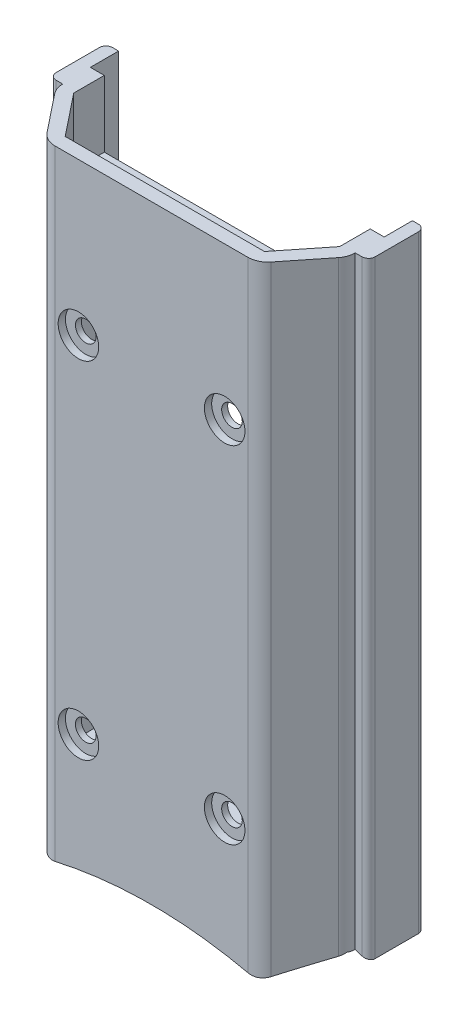
SolidWorks part; units mm, degrees
ref_plane "前视基准面" through (0, 0, 0) normal (0, 0, 1) x (1, 0, 0)
ref_plane "上视基准面" through (0, 0, 0) normal (0, 1, 0) x (1, 0, 0)
ref_plane "右视基准面" through (0, 0, 0) normal (1, 0, 0) x (0, 0, -1)
other "Configuration Table"
sketch "草图1" plane through (0, 0, 0) normal (0, 1, 0) x (1, 0, 0)
  line L5 (21.3466, -10.7196) -> (16.852, -16.3628)
  line L7 (20, -4.6001) -> (22, -4.6001)
  line L9 (20, -9.2001) -> (20, -4.6001)
  line L10 (14.9873, -15.4937) -> (20, -9.2001)
  line L11 (14.5054, -17.4937) -> (-14.5054, -17.4937)
  line L12 (-14.9873, -15.4937) -> (14.9873, -15.4937)
  line L14 (-20, -9.2001) -> (-14.9873, -15.4937)
  line L15 (-20, -4.6001) -> (-20, -9.2001)
  line L17 (-22.1, -0.3496) -> (-23, -0.3496)
  line L18 (-24, -1.3496) -> (-24, -7.8505)
  line L20 (-22, -4.6001) -> (-22.1, -4.6001)
  line L21 (-22.1, -4.6001) -> (-22.1, -0.3496)
  line L22 (22.1, -0.3496) -> (23, -0.3496)
  line L23 (24, -1.3496) -> (24, -7.8505)
  line L41 (22, -4.6001) -> (22.1, -4.6001)
  line L42 (22.1, -4.6001) -> (22.1, -0.3496)
  line L43 (-16.852, -16.3628) -> (-21.3466, -10.7196)
  line L57 (-22, -4.6001) -> (-20, -4.6001)
  line L59 (-22, -8.8505) -> (-23, -8.8505)
  line L61 (22, -8.8505) -> (23, -8.8505)
  arc A2 (23, -8.8505) -> (24, -7.8505) centre (23, -7.8505) ccw
  arc A3 (24, -1.3496) -> (23, -0.3496) centre (23, -1.3496) ccw
  arc A12 (16.852, -16.3628) -> (14.5054, -17.4937) centre (14.5054, -14.4937) cw
  arc A14 (-14.5054, -17.4937) -> (-16.852, -16.3628) centre (-14.5054, -14.4937) cw
  arc A16 (-23, -8.8505) -> (-24, -7.8505) centre (-23, -7.8505) cw
  arc A17 (-23, -0.3496) -> (-24, -1.3496) centre (-23, -1.3496) ccw
  arc A19 (21.3466, -10.7196) -> (22, -8.8505) centre (19, -8.8505) ccw
  arc A20 (-22, -8.8505) -> (-21.3466, -10.7196) centre (-19, -8.8505) ccw
  dimension "D3" = 0.1
  dimension "D2" = 0.1
extrude "凸台-拉伸1" add sketch "草图1" along normal up to surface (58.8974 mm away)
sketch "草图2" plane through (0, 0, 0) normal (0, -1, 0) x (1, 0, 0)
  line L18 (23, 8.8505) -> (22, 8.8505)
  line L19 (-24, 7.8505) -> (-24, 1.3496)
  line L20 (-23, 0.3496) -> (-22.1, 0.3496)
  line L21 (-22.1, 0.3496) -> (-22.1, 4.6001)
  line L22 (-22.1, 4.6001) -> (-20, 4.6001)
  line L23 (-20, 4.6001) -> (-20, 9.2001)
  line L24 (-20, 9.2001) -> (-14.9873, 15.4937)
  line L25 (-14.9873, 15.4937) -> (14.9873, 15.4937)
  line L26 (14.9873, 15.4937) -> (20, 9.2001)
  line L27 (20, 9.2001) -> (20, 4.6001)
  line L28 (20, 4.6001) -> (22.1, 4.6001)
  line L29 (22.1, 4.6001) -> (22.1, 0.3496)
  line L30 (22.1, 0.3496) -> (23, 0.3496)
  line L31 (24, 1.3496) -> (24, 7.8505)
  line L32 (23, 8.8505) -> (22, 8.8505)
  line L33 (21.3466, 10.7196) -> (16.852, 16.3628)
  line L34 (14.5054, 17.4937) -> (-14.5054, 17.4937)
  line L37 (-24, 7.8505) -> (-24, 1.3496)
  line L38 (-23, 0.3496) -> (-22.1, 0.3496)
  line L39 (-22.1, 0.3496) -> (-22.1, 4.6001)
  line L40 (-22.1, 4.6001) -> (-20, 4.6001)
  line L41 (-20, 4.6001) -> (-20, 9.2001)
  line L42 (-20, 9.2001) -> (-14.9873, 15.4937)
  line L43 (-14.9873, 15.4937) -> (14.9873, 15.4937)
  line L44 (14.9873, 15.4937) -> (20, 9.2001)
  line L45 (20, 9.2001) -> (20, 4.6001)
  line L46 (20, 4.6001) -> (22.1, 4.6001)
  line L47 (22.1, 4.6001) -> (22.1, 0.3496)
  line L48 (22.1, 0.3496) -> (23, 0.3496)
  line L49 (24, 1.3496) -> (24, 7.8505)
  line L51 (21.3466, 10.7196) -> (16.852, 16.3628)
  line L52 (14.5054, 17.4937) -> (-14.5054, 17.4937)
  line L57 (-16.852, 16.3628) -> (-21.3466, 10.7196)
  line L58 (-16.852, 16.3628) -> (-21.3466, 10.7196)
  line L61 (-22, 8.8505) -> (-23, 8.8505)
  line L62 (-22, 8.8505) -> (-23, 8.8505)
  arc A8 (-21.3466, 10.7196) -> (-22, 8.8505) centre (-19, 8.8505) ccw
  arc A9 (-21.3466, 10.7196) -> (-22, 8.8505) centre (-19, 8.8505) ccw
  arc A10 (22, 8.8505) -> (21.3466, 10.7196) centre (19, 8.8505) ccw
  arc A11 (22, 8.8505) -> (21.3466, 10.7196) centre (19, 8.8505) ccw
  arc A12 (-23, 8.8505) -> (-24, 7.8505) centre (-23, 7.8505) ccw
  arc A13 (-24, 1.3496) -> (-23, 0.3496) centre (-23, 1.3496) ccw
  arc A14 (23, 0.3496) -> (24, 1.3496) centre (23, 1.3496) ccw
  arc A15 (24, 7.8505) -> (23, 8.8505) centre (23, 7.8505) ccw
  arc A18 (16.852, 16.3628) -> (14.5054, 17.4937) centre (14.5054, 14.4937) ccw
  arc A19 (-14.5054, 17.4937) -> (-16.852, 16.3628) centre (-14.5054, 14.4937) ccw
  arc A22 (-23, 8.8505) -> (-24, 7.8505) centre (-23, 7.8505) ccw
  arc A23 (-24, 1.3496) -> (-23, 0.3496) centre (-23, 1.3496) ccw
  arc A24 (23, 0.3496) -> (24, 1.3496) centre (23, 1.3496) ccw
  arc A25 (24, 7.8505) -> (23, 8.8505) centre (23, 7.8505) ccw
  arc A28 (16.852, 16.3628) -> (14.5054, 17.4937) centre (14.5054, 14.4937) ccw
  arc A29 (-14.5054, 17.4937) -> (-16.852, 16.3628) centre (-14.5054, 14.4937) ccw
  dimension "D1" = 0
extrude "凸台-拉伸2" add sketch "草图2" along normal up to surface (38.3996 mm away)
ref_plane "基准面1" through (0, -38.3996, 0) normal (0, -1, 0) x (-1, 0, 0)
sketch "草图3" plane through (0, 0, 4.6001) normal (0, 0, -1) x (-1, 0, 0)
  line L0 (22.1, -38.3996) -> (22.1, -35.3996)
  line L1 (22.1, 58.8974) -> (22.1, -38.3996) construction
  line L2 (22.1, -35.3996) -> (-22.1, -35.3996)
  line L3 (-22.1, 58.8974) -> (-22.1, -38.3996) construction
  line L4 (-22.1, -35.3996) -> (-22.1, -38.3996)
  line L5 (-22.1, -38.3996) -> (22.1, -38.3996)
  dimension "D1" = 3
extrude "凸台-拉伸3" add sketch "草图3" against normal up to surface (12.8937 mm away) up to face at (0, 10.2489, 17.4937)
sketch "草图4" plane through (0, 0, 4.6001) normal (0, 0, -1) x (-1, 0, 0)
  line L0 (22.1, 38.8974) -> (-22.1, 38.8974)
  line L3 (22.1, 58.8974) -> (22.1, -38.3996) construction
  line L4 (22.1, 38.8974) -> (22.1, 35.8974)
  line L7 (-22.1, 58.8974) -> (-22.1, -38.3996) construction
  line L8 (-22.1, 38.8974) -> (-22.1, 35.8974)
  line L9 (-22.1, 35.8974) -> (22.1, 35.8974)
  dimension "D2" = 3
extrude "凸台-拉伸4" add sketch "草图4" against normal up to surface (12.8937 mm away) up to face at (0, -12.5754, 17.4937)
sketch "草图5" plane through (0, 38.8974, 0) normal (0, 1, 0) x (1, 0, 0)
  line L3 (-22, -8.8505) -> (-22.1, -8.8505)
  line L4 (-22.1, -8.8505) -> (-22.1, -17.4937)
  line L5 (-22.1, -17.4937) -> (-14.5054, -17.4937)
  line L7 (-22.1, -8.8505) -> (-22.1, -17.4937)
  line L8 (-22.1, -17.4937) -> (-14.5054, -17.4937)
  line L9 (14.5054, -17.4937) -> (22.1, -17.4937)
  line L10 (22.1, -17.4937) -> (22.1, -8.8505)
  line L11 (21.3466, -10.7196) -> (16.852, -16.3628)
  line L12 (14.5054, -17.4937) -> (22.1, -17.4937)
  line L13 (22.1, -17.4937) -> (22.1, -8.8505)
  line L14 (21.3466, -10.7196) -> (16.852, -16.3628)
  line L17 (-22, -8.8505) -> (-22.1, -8.8505)
  line L18 (-16.852, -16.3628) -> (-21.3466, -10.7196)
  line L19 (-16.852, -16.3628) -> (-21.3466, -10.7196)
  line L22 (22.1, -8.8505) -> (22, -8.8505)
  line L23 (22.1, -8.8505) -> (22, -8.8505)
  arc A2 (-22, -8.8505) -> (-21.3466, -10.7196) centre (-19, -8.8505) ccw
  arc A3 (-16.852, -16.3628) -> (-14.5054, -17.4937) centre (-14.5054, -14.4937) ccw
  arc A4 (-22, -8.8505) -> (-21.3466, -10.7196) centre (-19, -8.8505) ccw
  arc A5 (21.3466, -10.7196) -> (22, -8.8505) centre (19, -8.8505) ccw
  arc A6 (-16.852, -16.3628) -> (-14.5054, -17.4937) centre (-14.5054, -14.4937) ccw
  arc A9 (14.5054, -17.4937) -> (16.852, -16.3628) centre (14.5054, -14.4937) ccw
  arc A10 (21.3466, -10.7196) -> (22, -8.8505) centre (19, -8.8505) ccw
  arc A12 (14.5054, -17.4937) -> (16.852, -16.3628) centre (14.5054, -14.4937) ccw
  dimension "D1" = 0
  dimension "D2" = 0
extrude "切除-拉伸1" cut sketch "草图5" against normal up to surface (77.297 mm away) contours A6 L8 L7 L17 A4 L19 | A12 L14 A10 L23 L13 L12 up to face at (0, -38.3996, 6.2118)
sketch "草图6" plane through (0, 38.8974, 0) normal (0, 1, 0) x (1, 0, 0)
  line L12 (8.0613, -11.7949) -> (8.0613, -7.4001)
  line L13 (8.0613, -7.4001) -> (-8.0613, -7.4001)
  line L14 (-8.0613, -7.4001) -> (-8.0613, -11.7949)
  line L15 (-8.0613, -11.7949) -> (8.0613, -11.7949)
extrude "切除-拉伸2" cut sketch "草图6" against normal up to surface (3 mm away) up to face at (0, 35.8974, 9.7646)
sketch "草图7" plane through (0, -38.3996, 0) normal (0, -1, 0) x (-1, 0, 0)
  line L20 (20, -4.6001) -> (20, -9.2001)
  line L21 (22, -4.6001) -> (20, -4.6001)
  line L22 (22.1, -4.6001) -> (22, -4.6001)
  line L23 (22.1, -0.3496) -> (22.1, -4.6001)
  line L24 (23, -0.3496) -> (22.1, -0.3496)
  line L25 (24, -7.8505) -> (24, -1.3496)
  line L26 (22, -8.8505) -> (23, -8.8505)
  line L27 (16.852, -16.3628) -> (21.3466, -10.7196)
  line L28 (-14.5054, -17.4937) -> (14.5054, -17.4937)
  line L29 (-21.3466, -10.7196) -> (-16.852, -16.3628)
  line L30 (-23, -8.8505) -> (-22, -8.8505)
  line L31 (-24, -1.3496) -> (-24, -7.8505)
  line L32 (-22.1, -0.3496) -> (-23, -0.3496)
  line L33 (-22.1, -4.6001) -> (-22.1, -0.3496)
  line L34 (-22, -4.6001) -> (-22.1, -4.6001)
  line L35 (-20, -4.6001) -> (-22, -4.6001)
  line L36 (-20, -9.2001) -> (-20, -4.6001)
  line L37 (-14.9873, -15.4937) -> (-20, -9.2001)
  line L38 (14.9873, -15.4937) -> (-14.9873, -15.4937)
  line L39 (20, -9.2001) -> (14.9873, -15.4937)
  line L40 (20, -4.6001) -> (20, -9.2001)
  line L41 (22, -4.6001) -> (20, -4.6001)
  line L42 (22.1, -4.6001) -> (22, -4.6001)
  line L43 (22.1, -0.3496) -> (22.1, -4.6001)
  line L44 (23, -0.3496) -> (22.1, -0.3496)
  line L45 (24, -7.8505) -> (24, -1.3496)
  line L46 (22, -8.8505) -> (23, -8.8505)
  line L47 (16.852, -16.3628) -> (21.3466, -10.7196)
  line L48 (-14.5054, -17.4937) -> (14.5054, -17.4937)
  line L49 (-21.3466, -10.7196) -> (-16.852, -16.3628)
  line L50 (-23, -8.8505) -> (-22, -8.8505)
  line L51 (-24, -1.3496) -> (-24, -7.8505)
  line L52 (-22.1, -0.3496) -> (-23, -0.3496)
  line L53 (-22.1, -4.6001) -> (-22.1, -0.3496)
  line L54 (-22, -4.6001) -> (-22.1, -4.6001)
  line L55 (-20, -4.6001) -> (-22, -4.6001)
  line L56 (-20, -9.2001) -> (-20, -4.6001)
  line L57 (-14.9873, -15.4937) -> (-20, -9.2001)
  line L58 (14.9873, -15.4937) -> (-14.9873, -15.4937)
  line L59 (20, -9.2001) -> (14.9873, -15.4937)
  arc A8 (24, -1.3496) -> (23, -0.3496) centre (23, -1.3496) ccw
  arc A9 (23, -8.8505) -> (24, -7.8505) centre (23, -7.8505) ccw
  arc A10 (21.3466, -10.7196) -> (22, -8.8505) centre (19, -8.8505) ccw
  arc A11 (14.5054, -17.4937) -> (16.852, -16.3628) centre (14.5054, -14.4937) ccw
  arc A12 (-16.852, -16.3628) -> (-14.5054, -17.4937) centre (-14.5054, -14.4937) ccw
  arc A13 (-22, -8.8505) -> (-21.3466, -10.7196) centre (-19, -8.8505) ccw
  arc A14 (-24, -7.8505) -> (-23, -8.8505) centre (-23, -7.8505) ccw
  arc A15 (-23, -0.3496) -> (-24, -1.3496) centre (-23, -1.3496) ccw
  arc A16 (24, -1.3496) -> (23, -0.3496) centre (23, -1.3496) ccw
  arc A17 (23, -8.8505) -> (24, -7.8505) centre (23, -7.8505) ccw
  arc A18 (21.3466, -10.7196) -> (22, -8.8505) centre (19, -8.8505) ccw
  arc A19 (14.5054, -17.4937) -> (16.852, -16.3628) centre (14.5054, -14.4937) ccw
  arc A20 (-16.852, -16.3628) -> (-14.5054, -17.4937) centre (-14.5054, -14.4937) ccw
  arc A21 (-22, -8.8505) -> (-21.3466, -10.7196) centre (-19, -8.8505) ccw
  arc A22 (-24, -7.8505) -> (-23, -8.8505) centre (-23, -7.8505) ccw
  arc A23 (-23, -0.3496) -> (-24, -1.3496) centre (-23, -1.3496) ccw
  dimension "D1" = 0
extrude "凸台-拉伸5" add sketch "草图7" along normal blind 15
sketch "草图8" plane through (0, 0, 0) normal (1, 0, 0) x (0, 0, -1)
  line L14 (-9.8992, -38.2996) -> (-20.2915, -44.2996)
  line L18 (-9.8992, -40.3996) -> (-9.8992, -176.3996) construction
  line L19 (-20.2915, -44.3996) -> (-20.2915, -172.3996) construction
  line L20 (-20.2915, -44.2996) -> (-20.2915, -55.8019)
  line L21 (-9.8992, -108.3996) -> (14.8215, -108.3996) construction
  line L22 (-20.2915, -46.3996) -> (-20.2915, -170.3996) construction
  line L23 (-20.2915, -55.8019) -> (11.0914, -55.8019)
  line L25 (0.6991, -38.2996) -> (-9.8992, -38.2996)
  line L26 (-4.6001, 35.8974) -> (-4.6001, -35.3996) construction
  line L27 (11.0914, -44.2996) -> (11.0914, -55.8019)
  line L28 (0.6991, -38.2996) -> (11.0914, -44.2996)
revolve "切除-旋转1" cut sketch "草图8" angle 360 about L21
sketch "草图11" plane through (0, 0, 17.4937) normal (0, 0, 1) x (1, 0, 0)
  circle A0 centre (-11, 26.0001) radius 3.05
  circle A1 centre (11, 26.0001) radius 3.05
  circle A2 centre (-11, -26.0001) radius 3.05
  circle A3 centre (11, -26.0001) radius 3.05
extrude "切除-拉伸4" cut sketch "草图11" against normal blind 1.1
sketch "草图13" plane through (0, 58.8974, 0) normal (0, 1, 0) x (1, 0, 0)
  line L18 (-23, -8.8505) -> (-22, -8.8505)
  line L19 (-21.3466, -10.7196) -> (-16.852, -16.3628)
  line L20 (-14.5054, -17.4937) -> (14.5054, -17.4937)
  line L21 (16.852, -16.3628) -> (21.3466, -10.7196)
  line L22 (22, -8.8505) -> (23, -8.8505)
  line L23 (24, -7.8505) -> (24, -1.3496)
  line L24 (23, -0.3496) -> (22.1, -0.3496)
  line L25 (22.1, -0.3496) -> (22.1, -4.6001)
  line L26 (22.1, -4.6001) -> (20, -4.6001)
  line L27 (20, -4.6001) -> (20, -9.2001)
  line L28 (20, -9.2001) -> (14.9873, -15.4937)
  line L29 (14.9873, -15.4937) -> (-14.9873, -15.4937)
  line L30 (-14.9873, -15.4937) -> (-20, -9.2001)
  line L31 (-20, -9.2001) -> (-20, -4.6001)
  line L32 (-20, -4.6001) -> (-22.1, -4.6001)
  line L33 (-22.1, -4.6001) -> (-22.1, -0.3496)
  line L34 (-22.1, -0.3496) -> (-23, -0.3496)
  line L35 (-24, -1.3496) -> (-24, -7.8505)
  line L36 (-23, -8.8505) -> (-22, -8.8505)
  line L37 (-21.3466, -10.7196) -> (-16.852, -16.3628)
  line L38 (-14.5054, -17.4937) -> (14.5054, -17.4937)
  line L39 (16.852, -16.3628) -> (21.3466, -10.7196)
  line L40 (22, -8.8505) -> (23, -8.8505)
  line L41 (24, -7.8505) -> (24, -1.3496)
  line L42 (23, -0.3496) -> (22.1, -0.3496)
  line L43 (22.1, -0.3496) -> (22.1, -4.6001)
  line L44 (22.1, -4.6001) -> (20, -4.6001)
  line L45 (20, -4.6001) -> (20, -9.2001)
  line L46 (20, -9.2001) -> (14.9873, -15.4937)
  line L47 (14.9873, -15.4937) -> (-14.9873, -15.4937)
  line L48 (-14.9873, -15.4937) -> (-20, -9.2001)
  line L49 (-20, -9.2001) -> (-20, -4.6001)
  line L50 (-20, -4.6001) -> (-22.1, -4.6001)
  line L51 (-22.1, -4.6001) -> (-22.1, -0.3496)
  line L52 (-22.1, -0.3496) -> (-23, -0.3496)
  line L53 (-24, -1.3496) -> (-24, -7.8505)
  arc A8 (-22, -8.8505) -> (-21.3466, -10.7196) centre (-19, -8.8505) ccw
  arc A9 (-16.852, -16.3628) -> (-14.5054, -17.4937) centre (-14.5054, -14.4937) ccw
  arc A10 (14.5054, -17.4937) -> (16.852, -16.3628) centre (14.5054, -14.4937) ccw
  arc A11 (21.3466, -10.7196) -> (22, -8.8505) centre (19, -8.8505) ccw
  arc A12 (23, -8.8505) -> (24, -7.8505) centre (23, -7.8505) ccw
  arc A13 (24, -1.3496) -> (23, -0.3496) centre (23, -1.3496) ccw
  arc A14 (-23, -0.3496) -> (-24, -1.3496) centre (-23, -1.3496) ccw
  arc A15 (-24, -7.8505) -> (-23, -8.8505) centre (-23, -7.8505) ccw
  arc A16 (-22, -8.8505) -> (-21.3466, -10.7196) centre (-19, -8.8505) ccw
  arc A17 (-16.852, -16.3628) -> (-14.5054, -17.4937) centre (-14.5054, -14.4937) ccw
  arc A18 (14.5054, -17.4937) -> (16.852, -16.3628) centre (14.5054, -14.4937) ccw
  arc A19 (21.3466, -10.7196) -> (22, -8.8505) centre (19, -8.8505) ccw
  arc A20 (23, -8.8505) -> (24, -7.8505) centre (23, -7.8505) ccw
  arc A21 (24, -1.3496) -> (23, -0.3496) centre (23, -1.3496) ccw
  arc A22 (-23, -0.3496) -> (-24, -1.3496) centre (-23, -1.3496) ccw
  arc A23 (-24, -7.8505) -> (-23, -8.8505) centre (-23, -7.8505) ccw
  dimension "D1" = 0
extrude "切除-拉伸5" cut sketch "草图13" against normal blind 10
sketch "草图14" plane through (0, 0, 16.3937) normal (0, 0, 1) x (1, 0, 0)
  circle A0 centre (-11, 26.0001) radius 1.55
  circle A1 centre (11, 26.0001) radius 1.55
  circle A2 centre (-11, -26.0001) radius 1.55
  circle A3 centre (11, -26.0001) radius 1.55
extrude "切除-拉伸6" cut sketch "草图14" against normal through all
